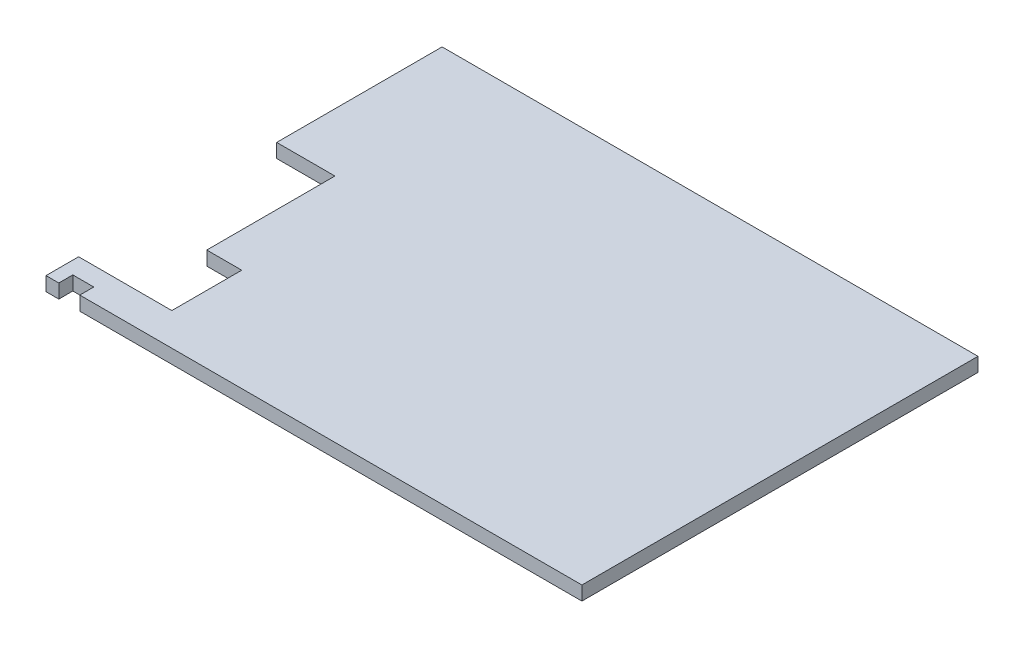
SolidWorks part; units mm, degrees
material "Acrilico TEC"
ref_plane "Front Plane" through (0, 0, 0) normal (0, 0, 1) x (1, 0, 0)
ref_plane "Top Plane" through (0, 0, 0) normal (0, 1, 0) x (1, 0, 0)
ref_plane "Right Plane" through (0, 0, 0) normal (1, 0, 0) x (0, 0, -1)
sketch "Sketch1" plane through (0, 0, 0) normal (0, 1, 0) x (1, 0, 0)
  line L0 (14.5, 4.7967) -> (230, 4.7967)
  line L1 (0, 4.7967) -> (5.5, 4.7967)
  line L2 (0, 103.7967) -> (0, 174.7967)
  line L3 (0, 174.7967) -> (230, 174.7967)
  line L4 (230, 4.7967) -> (230, 174.7967)
  line L6 (5.5, 4.7967) -> (5.5, 10.7967)
  line L7 (18.8044, 18.7967) -> (25, 18.7967)
  line L8 (25, 48.7967) -> (25, 103.7967)
  line L9 (25, 103.7967) -> (0, 103.7967)
  line L10 (25, 18.7967) -> (40, 18.7967)
  line L11 (40, 18.7967) -> (40, 48.7967)
  line L12 (40, 48.7967) -> (25, 48.7967)
  line L13 (0, 4.7967) -> (0, 18.7967)
  line L14 (0, 18.7967) -> (18.8044, 18.7967)
  line L15 (5.5, 10.7967) -> (14.5, 10.7967)
  line L16 (14.5, 4.7967) -> (14.5, 10.7967)
  dimension "D2" = 170
  dimension "D3" = 230
  dimension "D4" = 9
  dimension "D5" = 25
  dimension "D6" = 85
  dimension "D7" = 14
  dimension "D8" = 15
  dimension "D9" = 30
  dimension "D10" = 15
  dimension "D11" = 6.1956
  dimension "D12" = 6
  dimension "D13" = 5.5
extrude "Boss-Extrude1" add sketch "Sketch1" along normal blind 6
